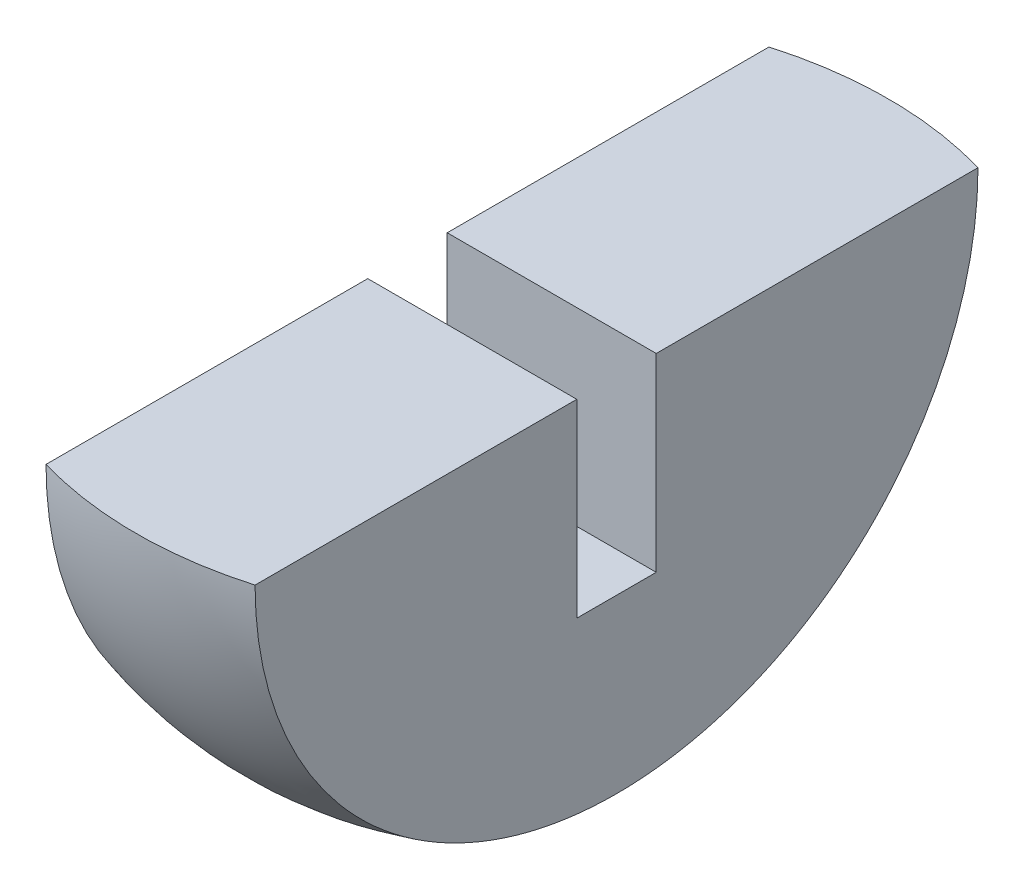
SolidWorks part; units mm, degrees
ref_plane "Front Plane" through (0, 0, 0) normal (0, 0, 1) x (1, 0, 0)
ref_plane "Top Plane" through (0, 0, 0) normal (0, 1, 0) x (1, 0, 0)
ref_plane "Right Plane" through (0, 0, 0) normal (1, 0, 0) x (0, 0, -1)
sketch "Sketch1" plane through (0, 0, 0) normal (0, 0, 1) x (1, 0, 0)
  line L0 (0, 0) -> (0, 135) construction
  line L1 (0, 0) -> (0, -135)
  line L2 (0, -135) -> (0, 135)
  line L3 (0, 0) -> (135, 0)
  arc A0 (0, -135) -> (0, 135) centre (0, 0) ccw
revolve "Revolve2" add sketch "Sketch1" angle 360 about L0 region at (57.2958, -57.2958, 0)
ref_plane "Plane1" through (0, 0, 135) normal (0, 0, 1) x (1, 0, 0)
sketch "Sketch2" plane through (0, 0, 135) normal (0, 0, 1) x (1, 0, 0)
  line L0 (-37.5, 0) -> (0, 0)
  line L1 (135, 0) -> (-135, 0) construction
  line L2 (-37.5, 0) -> (-37.5, -129.6871)
  line L3 (0, 0) -> (0, 32.2753) construction
  line L4 (37.5, 0) -> (37.5, -129.6871)
  line L5 (0, 0) -> (37.5, 0)
  arc A0 (-135, 0) -> (135, 0) centre (0, 0) ccw construction
  circle A1 centre (0, 0) radius 135
  dimension "D2" = 97.5
  dimension "D3" = 90
extrude "Cut-Extrude2" cut sketch "Sketch2" against normal through all contours L4 A1 L2 L0 L5 region at (0, 14.0886, 135)
sketch "Sketch3" plane through (0, 0, 0) normal (0, 1, 0) x (1, 0, 0)
  line L0 (0, 135) -> (0, -135) construction
  line L1 (-37.5, 129.6871) -> (37.5, 129.6871)
  line L2 (-37.5, 129.6871) -> (-37.5, -129.6871)
  line L3 (-37.5, -129.6871) -> (37.5, -129.6871)
  line L4 (37.5, 129.6871) -> (37.5, -129.6871)
  line L5 (-74.25, -135) -> (74.25, -135) construction
  line L7 (-37.5, 14.25) -> (37.5, 14.25)
  line L8 (-37.5, 14.25) -> (-37.5, -14.25)
  line L9 (-37.5, -14.25) -> (37.5, -14.25)
  line L10 (37.5, 14.25) -> (37.5, -14.25)
  arc A0 (37.5, 129.6871) -> (-37.5, 129.6871) centre (0, 0) ccw construction
  dimension "D1" = 28.5
  dimension "D2" = 120.75
extrude "Cut-Extrude3" cut sketch "Sketch3" against normal blind 68 contours L7 L0 L9 L4 | L0 L7 L2 L9 region at (18.75, 0, 0) region at (-18.75, 0, 0)
